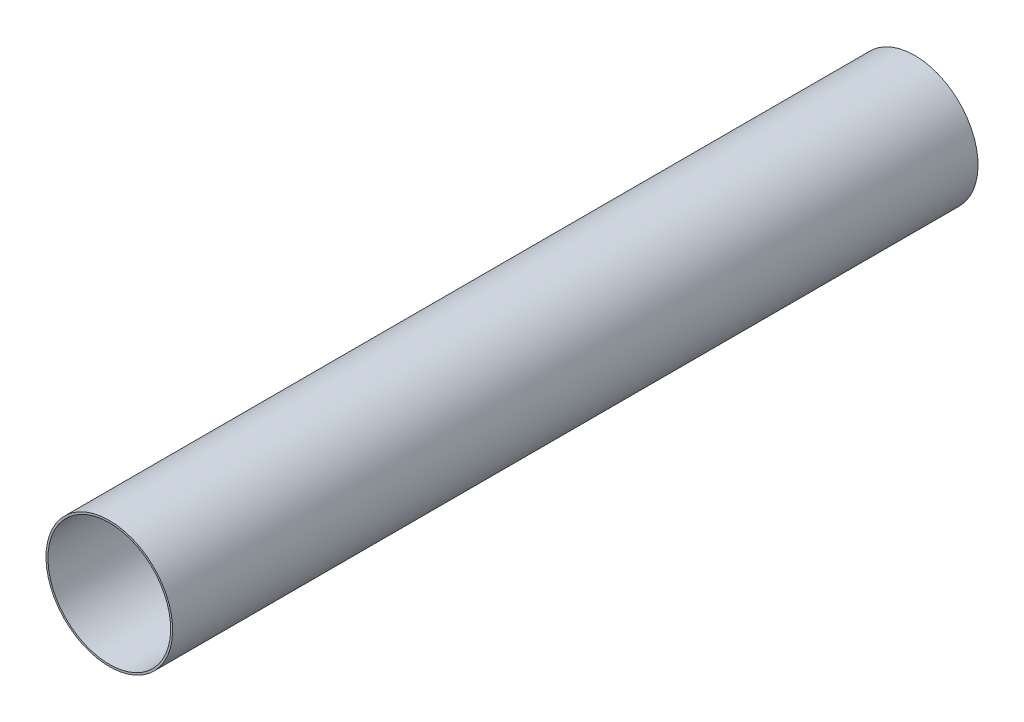
SolidWorks part; units mm, degrees
ref_plane "Plan de face" through (0, 0, 0) normal (0, 0, 1) x (1, 0, 0)
ref_plane "Plan de dessus" through (0, 0, 0) normal (0, 1, 0) x (1, 0, 0)
ref_plane "Plan de droite" through (0, 0, 0) normal (1, 0, 0) x (0, 0, -1)
sketch "Esquisse2" plane through (0, 0, 0) normal (1, 0, 0) x (0, 0, -1)
  line L0 (-10, 51.11) -> (-10, 49.53)
  line L2 (-10, 49.53) -> (-660, 49.53)
  line L19 (-660, 49.53) -> (-660, 51.11)
  line L20 (-660, 51.11) -> (-10, 51.11)
  line L24 (0, 0) -> (-694.9162, 0) construction
  dimension "D2" = 650
  dimension "D3" = 1.58
  dimension "D1" = 10
  dimension "D4" = 99.06
revolve "Révolution1" add sketch "Esquisse2" angle 360 about L24
equation "\"d_i_tube\"= 150mm'Inner Rocket Body Composite Tube Diameter"
equation "\"t_tube\"= 1.182mm'Thickness of Rocket Body Composite Tube"
equation "\"l_upper_body_tube\"= 1190mm'Upper Rocket Body Composite Tube length"
equation "\"l_lower_body_tube\"= 896mm'Lower Rocket Body Composite Tube Length"
equation "\"d_a_NC\"= 154mm'Outer Diameter of Nosecone base"
equation "\"d_i_phenolic_tube\"= 152.3mm'Inner Phenolic Tube Diameter"
equation "\"t_phenolic_tube\"= 2mm'Thickness of Phenolic Body Tube"
equation "\"l_fin_cut\"= 150mm'Length of fin on Motor Retainer"
equation "\"t_SW-Panel\"= 11.482mm'Thickness of Sandwich-Panel"
equation "\"l_motor_tube\"=650mm'Length of phenolic motor tube"
equation "\"d_i_motor_tube\"=99.06mm'Inner diameter of phenolic motor tube"
equation "\"t_motor_tube\"=1.58mm'Thicknes of phenolic motor tube"
equation "\"D4@Esquisse2\"=\"d_i_motor_tube\""
equation "\"D3@Esquisse2\"=\"t_motor_tube\""
equation "\"D2@Esquisse2\"=\"l_motor_tube\""
